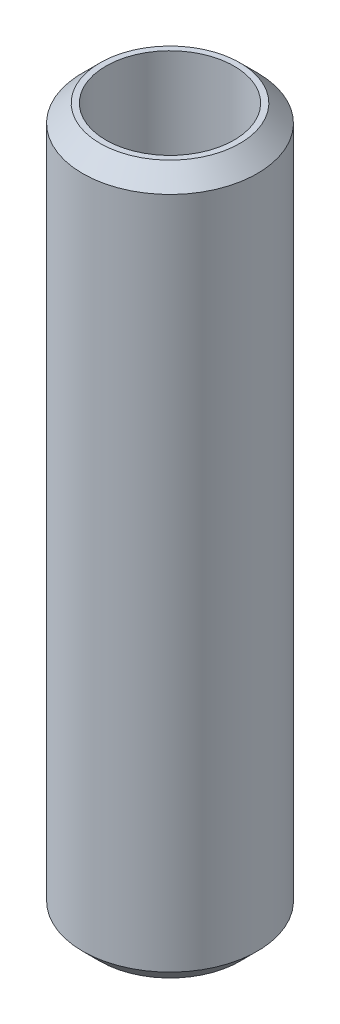
SolidWorks part; units mm, degrees
ref_plane "Front Plane" through (0, 0, 0) normal (0, 0, 1) x (1, 0, 0)
ref_plane "Top Plane" through (0, 0, 0) normal (0, 1, 0) x (1, 0, 0)
ref_plane "Right Plane" through (0, 0, 0) normal (1, 0, 0) x (0, 0, -1)
sketch "Sketch1" plane through (0, 0, 0) normal (0, 1, 0) x (1, 0, 0)
  circle A0 centre (0, 0) radius 25
  dimension "SHAFT_OD" = 50
extrude "Boss-Extrude1" add sketch "Sketch1" along normal blind 202.788
sketch "Sketch2" plane through (0, 0, 0) normal (0, 1, 0) x (1, 0, 0)
  circle A0 centre (0, 0) radius 18.3605
  dimension "BORE_D" = 36.721
extrude "Cut-Extrude1" cut sketch "Sketch2" along normal through all
chamfer "Chamfer1" distance 4.9832 angle 45 2 edges at (0, 202.788, 25) (0, 0, 25)
